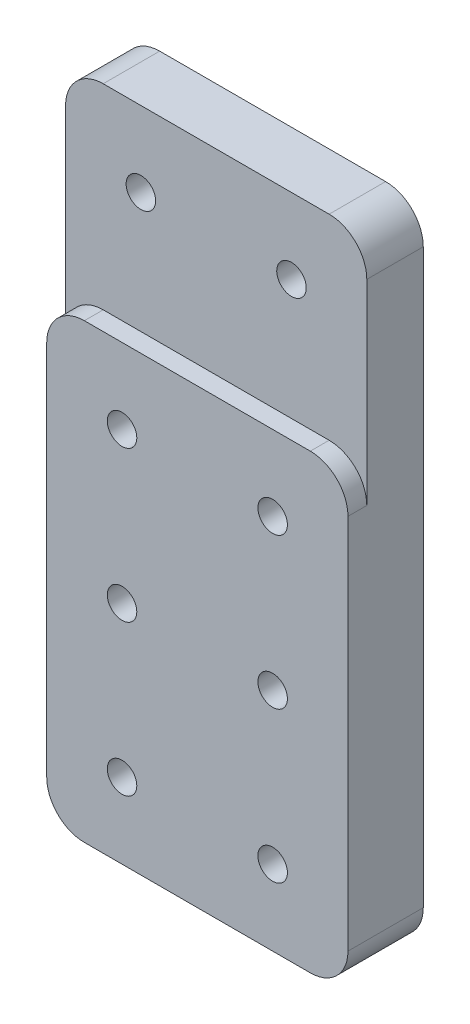
SolidWorks part; units mm, degrees
material "PET"
ref_plane "Front Plane" through (0, 0, 0) normal (0, 0, 1) x (1, 0, 0)
ref_plane "Top Plane" through (0, 0, 0) normal (0, 1, 0) x (1, 0, 0)
ref_plane "Right Plane" through (0, 0, 0) normal (1, 0, 0) x (0, 0, -1)
sketch "Sketch2" plane through (0, 0, 0) normal (0, 0, 1) x (1, 0, 0)
  line L1 (0, 0) -> (50.8, 0)
  line L2 (0, 0) -> (0, 109.22)
  line L3 (0, 109.22) -> (50.8, 109.22)
  line L4 (50.8, 0) -> (50.8, 109.22)
  dimension "D1" = 50.8
  dimension "D2" = 109.22
extrude "Boss-Extrude1" add sketch "Sketch2" against normal blind 12.7
sketch "Sketch3" plane through (0, 0, 0) normal (0, 0, 1) x (1, 0, 0)
  line L0 (50.8, 109.22) -> (0, 109.22) construction
  line L1 (0, 109.22) -> (0, 0) construction
  circle A0 centre (12.7, 96.52) radius 2.4892
  circle A17 centre (38.1, 96.52) radius 2.4892
  circle A24 centre (12.7, 63.5) radius 2.4892
  circle A25 centre (12.7, 38.1) radius 2.4892
  circle A26 centre (12.7, 12.7) radius 2.4892
  circle A27 centre (12.7, -12.7) radius 2.4892
  circle A28 centre (12.7, -38.1) radius 2.4892
  circle A29 centre (38.1, 38.1) radius 2.4892
  circle A30 centre (38.1, 12.7) radius 2.4892
  circle A31 centre (38.1, -12.7) radius 2.4892
  circle A32 centre (38.1, -38.1) radius 2.4892
  circle A33 centre (38.1, 63.5) radius 2.4892
  dimension "D1" = 4.9784
  dimension "D6" = 4.9784
  dimension "D2" = 12.7
  dimension "D3" = 12.7
  dimension "D7" = 12.7
  dimension "D8" = 33.02
  dimension "D4" = 1
  dimension "D5" = 2
  dimension "D9" = 5
  dimension "D10" = 2
extrude "Cut-Extrude1" cut sketch "Sketch3" against normal through all
fillet "Fillet1" radius 6.35 4 edges at (0, 0, -6.35) (50.8, 0, -6.35) (50.8, 109.22, -6.35) (0, 109.22, -6.35)
sketch "Sketch4" plane through (0, 0, 0) normal (-1, 0, 0) x (0, 0, 1)
  line L1 (-3.175, 109.22) -> (0, 109.22)
  line L2 (-3.175, 109.22) -> (-3.175, 76.2)
  line L3 (-3.175, 76.2) -> (0, 76.2)
  line L4 (0, 109.22) -> (0, 76.2)
  line L5 (0, 102.87) -> (0, 6.35) construction
  line L6 (-12.7, 109.22) -> (0, 109.22) construction
  dimension "D1" = 33.02
  dimension "D2" = 3.175
extrude "Cut-Extrude2" cut sketch "Sketch4" against normal through all
fillet "Fillet3" radius 6.35 2 edges at (50.8, 76.2, -1.5875) (0, 76.2, -1.5875)
